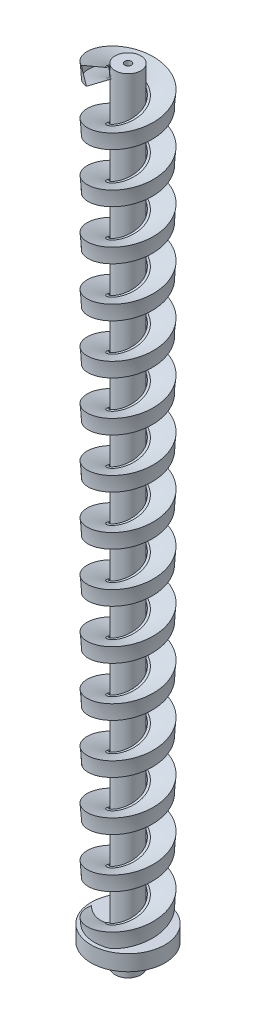
SolidWorks part; units mm, degrees
ref_plane "Front Plane" through (0, 0, 0) normal (0, 0, 1) x (1, 0, 0)
ref_plane "Top Plane" through (0, 0, 0) normal (0, 1, 0) x (1, 0, 0)
ref_plane "Right Plane" through (0, 0, 0) normal (1, 0, 0) x (0, 0, -1)
sketch "Sketch1" plane through (0, 0, 0) normal (0, 1, 0) x (1, 0, 0)
  circle A0 centre (0, 0) radius 5.75
  circle A1 centre (0, 0) radius 2
  dimension "D1" = 11.5
  dimension "D2" = 4
extrude "Boss-Extrude1" add sketch "Sketch1" along normal blind 340 contours A0 A1 | A1 region at (-5.5874, 0, 0) region at (0, 0, 0)
ref_plane "Plane3" through (0, 340, 0) normal (0, 1, 0) x (1, 0, 0)
sketch "Sketch28" plane through (0, 0, 0) normal (0, -1, 0) x (1, 0, 0)
  circle A0 centre (0, 0) radius 5.75 construction
  circle A1 centre (0, 0) radius 5.75
curve "Helix/Spiral1" pitch 22.0921 height 335.8 turns 15.2
ref_plane "Plane4" through (-5.75, 0, 0) normal (0, 0.5217, 0.8531) x (1, 0, 0)
sketch "Sketch32" plane through (-5.75, 0, 0) normal (0, 0.5217, 0.8531) x (1, 0, 0)
  line L7 (-1, 4) -> (-9, 6.9118)
  line L8 (0, 0) -> (-1, 0)
  line L9 (0, 0) -> (0, 4)
  line L10 (0, 4) -> (-1, 4)
  line L12 (-9, 6.9118) -> (-9, 0)
  line L13 (-9, 0) -> (-1, 0)
  dimension "D1" = 4
  dimension "D2" = 1
  dimension "D3" = 8
  dimension "D4" = 20
  dimension "D5" = 4
surface "Surface-Sweep1"
sketch "Sketch33" plane through (0, 0, 0) normal (0, -1, 0) x (1, 0, 0)
  circle A0 centre (0, 0) radius 16.5
  dimension "D1" = 33
extrude "Boss-Extrude2" add sketch "Sketch33" against normal blind 7
extrude "Boss-Extrude5" add sketch "Sketch1<4>" against normal blind 10 contours A1 | A0 A1 region at (-5.5874, 0, 0) region at (0, 0, 0)
sketch "Sketch1<4>" plane through (0, 0, 0) normal (0, 1, 0) x (1, 0, 0) same geometry as "Sketch1"
sketch "Sketch38" plane through (0, -10, 0) normal (0, -1, 0) x (1, 0, 0)
  circle A0 centre (0, 0) radius 2.125
  dimension "D1" = 4.25
extrude "Cut-Extrude1" cut sketch "Sketch38" against normal blind 8
sketch "Sketch39" plane through (0, -2, 0) normal (0, -1, 0) x (1, 0, 0)
  line L0 (-1.3984, 1.6) -> (1.3984, 1.6)
  circle A0 centre (0, 0) radius 2.125 construction
  circle A1 centre (0, 0) radius 2.125
  circle M2 centre (0, 0) radius 2.125
  dimension "D1" = 1.6
extrude "Boss-Extrude6" add sketch "Sketch39" along normal up to surface (8 mm away) contours L0 M2 region at (0, -2, 1.8124) up to face at (0, -10, -2.125)
sketch "Sketch40" plane through (0, 340, 0) normal (0, 1, 0) x (1, 0, 0)
  circle A0 centre (0, 0) radius 1.5
  dimension "D1" = 3
extrude "Cut-Extrude2" cut sketch "Sketch40" against normal blind 10
